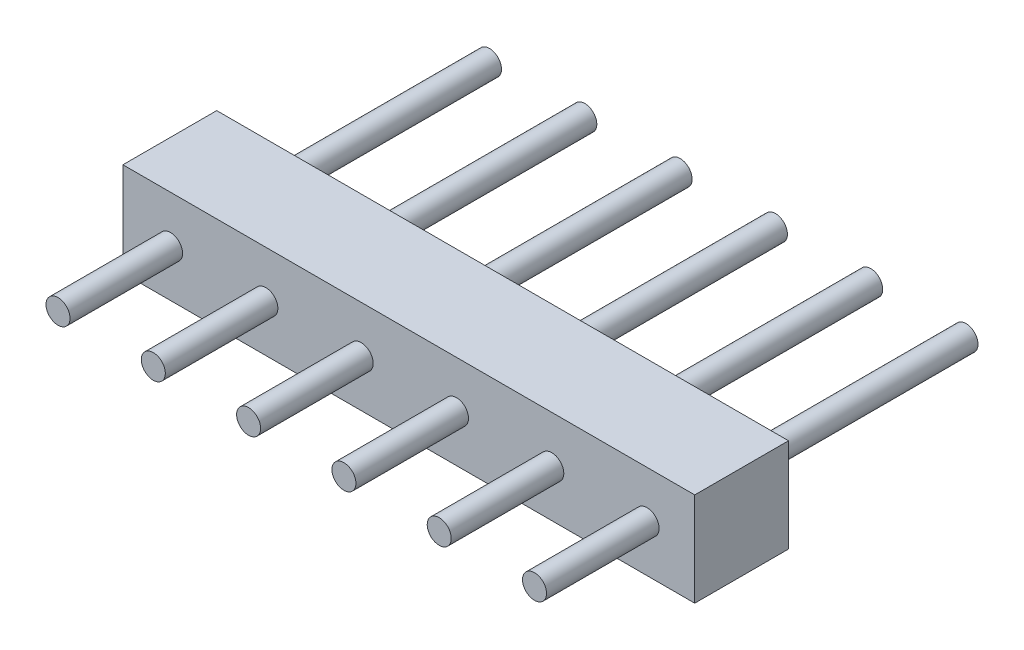
SolidWorks part; units mm, degrees
ref_plane "前视基准面" through (0, 0, 0) normal (0, 0, 1) x (1, 0, 0)
ref_plane "上视基准面" through (0, 0, 0) normal (0, 1, 0) x (1, 0, 0)
ref_plane "右视基准面" through (0, 0, 0) normal (1, 0, 0) x (0, 0, -1)
sketch "Sketch1" plane through (0, 0, 0) normal (0, 0, 1) x (1, 0, 0)
  line L1 (0, 0) -> (15.24, 0)
  line L2 (0, 0) -> (0, 2.5)
  line L3 (0, 2.5) -> (15.24, 2.5)
  line L4 (15.24, 0) -> (15.24, 2.5)
extrude "Boss-Extrude1" add sketch "Sketch1" along normal blind 2.5
sketch "Sketch2" plane through (0, 0, 2.5) normal (0, 0, 1) x (1, 0, 0)
  line L0 (0, 1.25) -> (16.6592, 1.25) construction
  line L1 (0, 2.5) -> (0, 0) construction
  line L2 (7.62, 2.5) -> (7.62, -1.2277) construction
  line L3 (15.24, 2.5) -> (0, 2.5) construction
  circle A0 centre (1.27, 1.25) radius 0.32
  circle A1 centre (3.81, 1.25) radius 0.32
  circle A2 centre (6.35, 1.25) radius 0.32
  circle A3 centre (8.89, 1.25) radius 0.32
  circle A4 centre (11.43, 1.25) radius 0.32
  circle A5 centre (13.97, 1.25) radius 0.32
  dimension "D1" = 0.64
  dimension "D2" = 6.35
  dimension "D3" = 6
extrude "Boss-Extrude2" add sketch "Sketch2" along normal blind 3
extrude "Boss-Extrude3" add sketch "Sketch2<2>" against normal blind 6 from surface starting at face at (7.62, 1.25, 0)
sketch "Sketch2<2>" plane through (0, 0, 2.5) normal (0, 0, 1) x (1, 0, 0) same geometry as "Sketch2"
